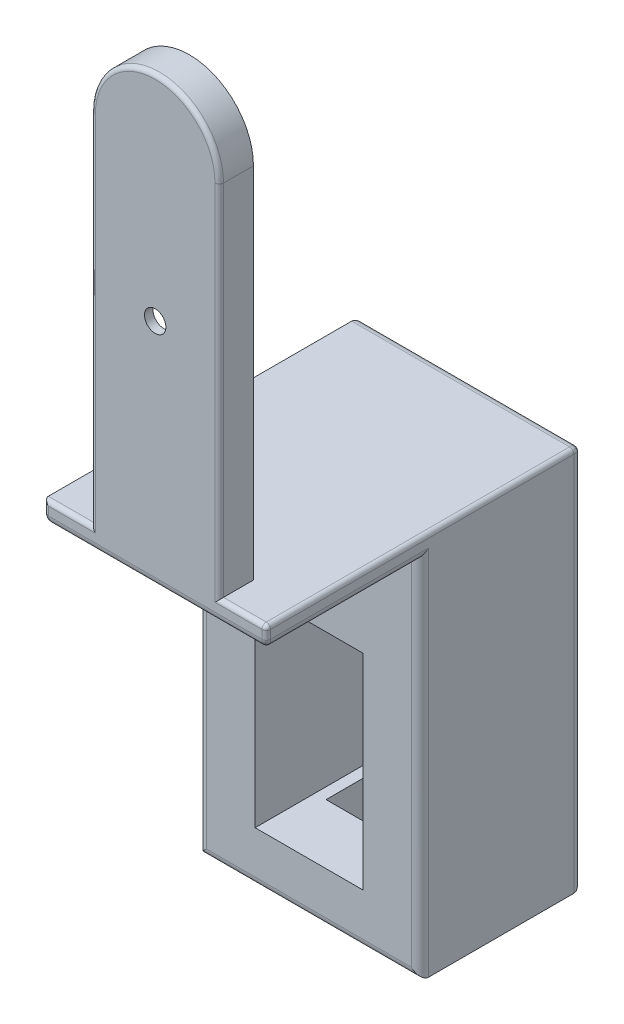
SolidWorks part; units mm, degrees
ref_plane "前基準面" through (0, 0, 0) normal (0, 0, 1) x (1, 0, 0)
ref_plane "上基準面" through (0, 0, 0) normal (0, 1, 0) x (1, 0, 0)
ref_plane "右基準面" through (0, 0, 0) normal (1, 0, 0) x (0, 0, -1)
sketch "草圖1" plane through (0, 0, 0) normal (0, 0, 1) x (1, 0, 0)
  line L1 (7.5, 10) -> (7.5, 52)
  line L3 (-7.5, 10) -> (-7.5, 52)
  line L4 (7.5, 10) -> (-7.5, 10)
  arc A0 (7.5, 52) -> (-7.5, 52) centre (0, 52) ccw
  dimension "D1" = 15
  dimension "D2" = 7.5
  dimension "D3" = 42
extrude "填料-伸長1" add sketch "草圖1" along normal blind 4
sketch "草圖3" plane through (0, 0, 0) normal (0, 0, 1) x (1, 0, 0)
  line L0 (0, 0) -> (0, 14.8578) construction
  line L1 (7.5, 52) -> (-7.5, 52) construction
  line L2 (7.5, 15) -> (-7.5, 15) construction
  line L3 (7.5, 10) -> (7.5, 52) construction
  line L4 (-7.5, 52) -> (-7.5, 10) construction
  line L6 (7.5, 34.5) -> (5, 34.5) construction
  line L7 (5, 34.5) -> (2.1147, 16.658)
  line L8 (5, 34.5) -> (2.1328, 52)
  line L9 (-2.1328, 52) -> (-5, 34.5)
  line L10 (-5, 34.5) -> (-2.1422, 17)
  line L11 (0, 54.1328) -> (0, 59.5) construction
  line L12 (-5, 34.5) -> (-7.5, 34.5) construction
  arc A0 (7.5, 52) -> (-7.5, 52) centre (0, 52) ccw construction
  arc A1 (-4.7386, 36.0956) -> (-4.7403, 32.9094) centre (0, 34.5) ccw
  arc A2 (-2.1422, 17) -> (2.1147, 16.658) centre (0, 17) ccw
  arc A3 (-2.1328, 52) -> (2.1328, 52) centre (0, 52) cw
  arc A4 (4.7452, 32.9241) -> (4.7386, 36.0956) centre (0, 34.5) ccw
  dimension "D4" = 10
  dimension "D1" = 35
extrude "除料-伸長1" cut sketch "草圖3" along normal blind 3 contours A3 L9 L10 A2 L7 L8
sketch "草圖5" plane through (0, 0, 0) normal (0, 0, 1) x (1, 0, 0)
  line L0 (5, 34.5) -> (-5, 34.5) construction
  circle A0 centre (0, 34.5) radius 1.25
  dimension "D1" = 2.5
extrude "除料-伸長2" cut sketch "草圖5" along normal blind 12.4
ref_plane "平面1" through (0, -35, 0) normal (0, 1, 0) x (1, 0, 0)
sketch "草圖13" plane through (0, 0, 4) normal (0, 0, 1) x (1, 0, 0)
  line L0 (0, 10) -> (0, -4.3971) construction
  line L1 (7.5, 10) -> (-7.5, 10) construction
  line L3 (-13, 10) -> (13, 10)
  line L4 (-13, 10) -> (-13, -35)
  line L5 (-13, -35) -> (13, -35)
  line L6 (13, 10) -> (13, -35)
  dimension "D1" = 45
  dimension "D2" = 45
  dimension "D3" = 13
  dimension "D4" = 13
ref_plane "平面2" through (0, 0, 4) normal (0, 0, 1) x (1, 0, 0)
extrude "填料-伸長2" add sketch "草圖13" against normal blind 37
sketch "草圖14" plane through (0, 0, 4) normal (0, 0, -1) x (-1, 0, 0)
  line L0 (0, 10) -> (0, -35) construction
  line L1 (-7.5, 10) -> (7.5, 10) construction
  line L2 (13, -35) -> (-13, -35) construction
  line L4 (-6.3, -5) -> (6.3, -5)
  line L5 (-6.3, -5) -> (-6.3, -29)
  line L6 (-6.3, -29) -> (6.3, -29)
  line L7 (6.3, -5) -> (6.3, -29)
  point P10 (0, -12.5)
  dimension "D1" = 6.3
  dimension "D2" = 6.3
  dimension "D3" = 24
  dimension "D4" = 6
ref_plane "平面4" through (0, 0, 4) normal (0, 0, 1) x (1, 0, 0)
extrude "除料-伸長3" cut sketch "草圖14" along normal blind 35
sketch "草圖15" plane through (0, 0, 4) normal (0, 0, 1) x (1, 0, 0)
  line L0 (0, -5) -> (0, -22.6416) construction
  line L1 (-6.3, -5) -> (6.3, -5) construction
  line L2 (0, -1.85) -> (0, -32.65) construction
  line L4 (6.3, -29) -> (-6.3, -29) construction
  circle A0 centre (0, -1.85) radius 1.15
  circle A1 centre (0, -32.65) radius 1.15
  dimension "D1" = 2.3
  dimension "D2" = 2.3
  dimension "D3" = 2
  dimension "D4" = 2.5
ref_plane "平面5" through (0, -35, 0) normal (0, -1, 0) x (-1, 0, 0)
sketch "草圖16" plane through (0, -35, 0) normal (0, -1, 0) x (-1, 0, 0)
  line L0 (0, 33) -> (0, 0) construction
  line L1 (13, 33) -> (-13, 33) construction
  line L3 (-5, 29) -> (5, 29)
  line L4 (-5, 29) -> (-5, 21)
  line L5 (-5, 21) -> (5, 21)
  line L6 (5, 29) -> (5, 21)
  dimension "D1" = 10
  dimension "D2" = 4
  dimension "D3" = 8
  dimension "D4" = 5
extrude "除料-伸長5" cut sketch "草圖16" against normal blind 8
sketch "草圖17" plane through (0, 0, 4) normal (0, 0, 1) x (1, 0, 0)
  line L0 (-13, 10) -> (-13, -35) construction
  line L1 (-13, 7.5) -> (13, 7.5)
  line L2 (-13, 7.5) -> (-13, -35)
  line L3 (-13, -35) -> (13, -35)
  line L4 (13, 7.5) -> (13, -35)
  line L5 (-14.3, -35) -> (14.3, -35) construction
  line L6 (13, -35) -> (13, 10) construction
  line L7 (7.5, 10) -> (-7.5, 10) construction
  dimension "D1" = 2.5
extrude "除料-伸長6" cut sketch "草圖17" against normal blind 18
fillet "圓角10" radius 1 4 edges at (0, 10, -33) (-13, -12.5, -33) (13, -12.5, -33) (0, -35, -33)
fillet "圓角12" radius 1 3 edges at (-13, 7.5, -5) (13, 7.5, -5) (0, 7.5, 4)
fillet "圓角13" radius 0.5 2 edges at (13, 10, -14) (12.7071, 9.7071, -32.7071)
fillet "圓角14" radius 0.5 10 edges at (13, 9, 4) (12.7071, 7.7929, 3.7071) (-12.7071, 7.7929, 3.7071) (7.5, 31, 4) (10, 10, 4) (12.8536, 9.8536, 4) (-13, 9.25, 4) (0, 59.5, 4) (-10.25, 10, 4) (-7.5, 31, 4)
fillet "圓角18" radius 1 5 edges at (12.7071, 7.7929, -14) (-12.7071, 7.7929, -14) (-13, -13.25, -14) (13, -13.25, -14) (0, -35, -14)
sketch "草圖18" plane through (13, 0, 0) normal (1, 0, 0) x (0, 0, -1)
